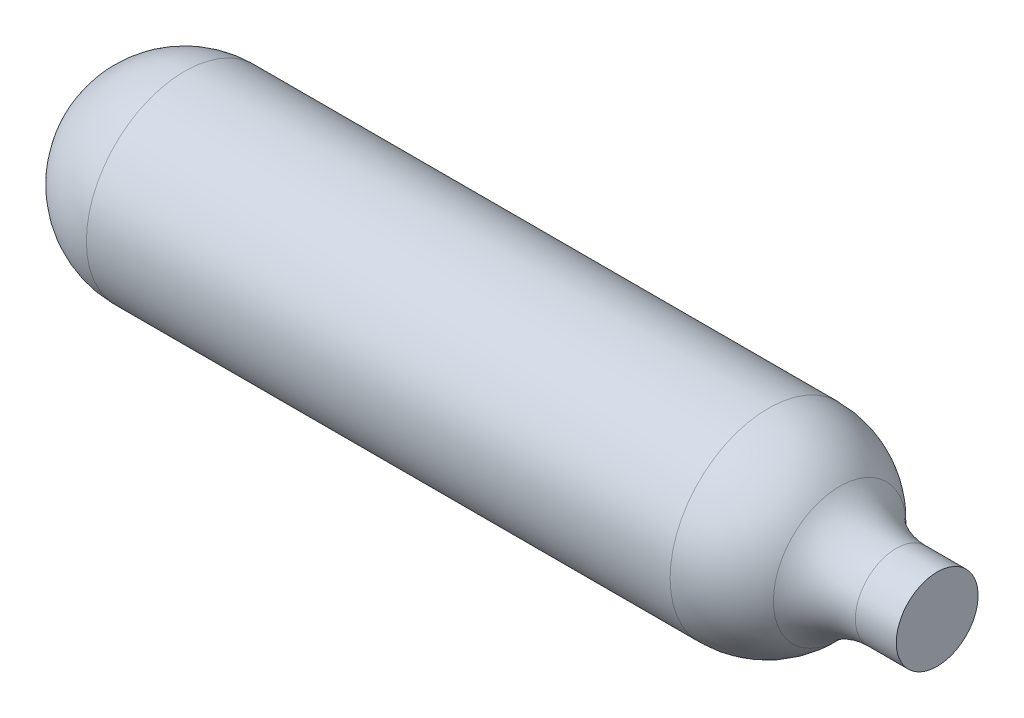
SolidWorks part; units mm, degrees
ref_plane "Front Plane" through (0, 0, 0) normal (0, 0, 1) x (1, 0, 0)
ref_plane "Top Plane" through (0, 0, 0) normal (0, 1, 0) x (1, 0, 0)
ref_plane "Right Plane" through (0, 0, 0) normal (1, 0, 0) x (0, 0, -1)
sketch "Sketch1" plane through (0, 0, 0) normal (0, 0, 1) x (1, 0, 0)
  line L0 (0, 0) -> (82.55, 0)
  line L1 (82.55, 0) -> (82.55, 3.9688)
  line L2 (82.55, 3.9688) -> (78.5812, 3.9687)
  line L3 (9.525, 9.525) -> (66.1617, 9.525)
  circle A0 centre (9.525, 0) radius 9.525
  arc A1 (66.1617, 9.525) -> (73.0857, 6.4273) centre (66.1617, 0.2377) cw
  arc A2 (73.0857, 6.4273) -> (78.5812, 3.9687) centre (78.5812, 11.3399) ccw
  dimension "D2" = 19.05
  dimension "D3" = 3.9688
  dimension "D1" = 82.55
  dimension "D4" = 3.9688
revolve "Revolve1" add sketch "Sketch1" angle 360 about L0 region at (9.525, 4.0425, 0) region at (47.0791, 4.6239, 0) other way angle 360
